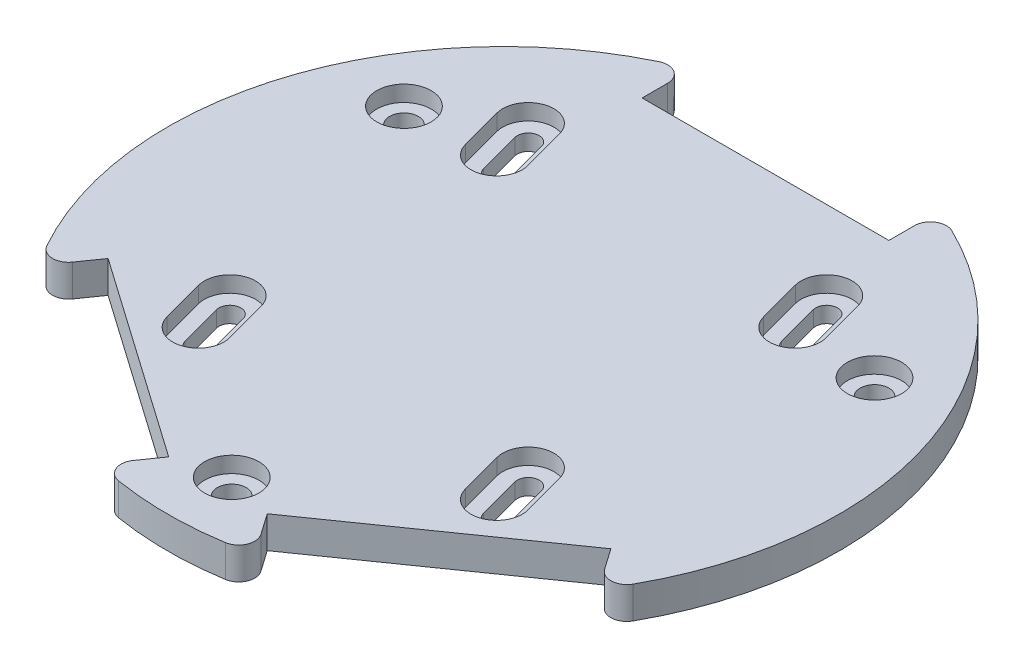
SolidWorks part; units mm, degrees
ref_plane "Plan de face" through (0, 0, 0) normal (0, 0, 1) x (1, 0, 0)
ref_plane "Plan de dessus" through (0, 0, 0) normal (0, 1, 0) x (1, 0, 0)
ref_plane "Plan de droite" through (0, 0, 0) normal (1, 0, 0) x (0, 0, -1)
sketch "Sketch1" plane through (0, 0, 0) normal (0, 1, 0) x (1, 0, 0)
  line L0 (0, 0) -> (0, 41) construction
  line L1 (0, 0) -> (-23.5166, -33.5852) construction
  line L2 (0, 0) -> (23.5166, -33.5852) construction
  line L3 (-39.3263, -22.5152) -> (-7.707, -44.6553)
  line L4 (7.707, -44.6553) -> (39.3263, -22.5152)
  line L5 (-19.3, 41) -> (19.3, 41)
  line L6 (-19.3, 41) -> (-19.3, 48.8238)
  line L8 (19.3, 41) -> (19.3, 48.8238)
  line L9 (7.707, -44.6553) -> (12.1945, -51.0641)
  line L11 (39.3263, -22.5152) -> (43.8138, -28.9241)
  line L12 (-7.707, -44.6553) -> (-12.1945, -51.0641)
  line L13 (-39.3263, -22.5152) -> (-43.8138, -28.9241)
  line L14 (0, 0) -> (0, -42.5) construction
  line L15 (0, 0) -> (-36.8061, 21.25) construction
  line L16 (0, 0) -> (36.8061, 21.25) construction
  arc A0 (-19.3, 48.8238) -> (-43.8138, -28.9241) centre (0, 0) ccw
  arc A1 (43.8138, -28.9241) -> (19.3, 48.8238) centre (0, 0) ccw
  circle A3 centre (-36.8061, 21.25) radius 2.25 construction
  circle A4 centre (36.8061, 21.25) radius 2.25 construction
  circle A6 centre (0, -42.5) radius 2.25 construction
  arc A7 (-12.1945, -51.0641) -> (12.1945, -51.0641) centre (0, 0) ccw
  circle A8 centre (-36.8061, 21.25) radius 4.25
  circle A9 centre (36.8061, 21.25) radius 4.25
  circle A10 centre (0, -42.5) radius 4.25
  point P25 (23.5166, -33.5852)
  point P26 (-23.5166, -33.5852)
  dimension "D1" = 105
  dimension "D5" = 35
  dimension "D6" = 38.6
  dimension "D10" = 4.5
  dimension "D4" = 8.5
  dimension "D9" = 42.5
  dimension "D2" = 35
  dimension "D3" = 41
  dimension "D7" = 120
  dimension "D8" = 120
extrude "Boss-Extrude1" add sketch "Sketch1" along normal blind 5 contours L4 A0 L5 L3 | A8 | A9 | A10 region at (0, 0, -1.6057) region at (-36.8061, 0, -21.25) region at (36.8061, 0, -21.25) region at (0, 0, 42.5)
sketch "Esquisse1" plane through (0, 5, 0) normal (0, 1, 0) x (1, 0, 0)
  line L0 (0, 0) -> (-23.3345, 23.3345) construction
  line L1 (0, 0) -> (0, 41) construction
  line L2 (-19.3, 41) -> (19.3, 41) construction
  line L3 (-24.758, 28.6471) -> (-22.9463, 21.8856) construction
  line L4 (-23.116, 29.0871) -> (-21.3042, 22.3256)
  line L5 (-26.4001, 28.2071) -> (-24.5884, 21.4456)
  line L6 (0, 0) -> (23.3345, 23.3345) construction
  line L7 (0, 0) -> (23.3345, -23.3345) construction
  line L8 (0, 0) -> (-23.3345, -23.3345) construction
  line L9 (23.7228, 21.8856) -> (21.911, 28.6471) construction
  line L10 (22.0807, 21.4456) -> (20.2689, 28.2071)
  line L11 (25.3648, 22.3256) -> (23.5531, 29.0871)
  line L12 (23.7228, -24.7834) -> (21.911, -18.0219) construction
  line L13 (22.0807, -25.2234) -> (20.2689, -18.4619)
  line L14 (25.3648, -24.3434) -> (23.5531, -17.5819)
  line L15 (-22.9463, -24.7834) -> (-24.758, -18.0219) construction
  line L16 (-24.5884, -25.2234) -> (-26.4001, -18.4619)
  line L17 (-21.3042, -24.3434) -> (-23.116, -17.5819)
  line L18 (0, 0) -> (-10.9859, 41) construction
  line L19 (-22.9463, 21.8856) -> (-24.758, 28.6471) construction
  line L20 (-26.81, 20.8504) -> (-28.6217, 27.6118)
  line L21 (-19.0826, 22.9209) -> (-20.8943, 29.6824)
  line L22 (23.7228, 21.8856) -> (21.911, 28.6471) construction
  line L23 (19.859, 20.8504) -> (18.0473, 27.6118)
  line L24 (27.5865, 22.9209) -> (25.7747, 29.6824)
  line L25 (23.7228, -24.7834) -> (21.911, -18.0219) construction
  line L26 (19.859, -25.8187) -> (18.0473, -19.0572)
  line L27 (27.5865, -23.7481) -> (25.7747, -16.9867)
  line L28 (-22.9463, -24.7834) -> (-24.758, -18.0219) construction
  line L29 (-26.81, -25.8187) -> (-28.6217, -19.0572)
  line L30 (-19.0826, -23.7481) -> (-20.8943, -16.9867)
  arc A0 (-23.116, 29.0871) -> (-26.4001, 28.2071) centre (-24.758, 28.6471) ccw
  arc A1 (-24.5884, 21.4456) -> (-21.3042, 22.3256) centre (-22.9463, 21.8856) ccw
  arc A2 (22.0807, 21.4456) -> (25.3648, 22.3256) centre (23.7228, 21.8856) ccw
  arc A3 (23.5531, 29.0871) -> (20.2689, 28.2071) centre (21.911, 28.6471) ccw
  arc A4 (22.0807, -25.2234) -> (25.3648, -24.3434) centre (23.7228, -24.7834) ccw
  arc A5 (23.5531, -17.5819) -> (20.2689, -18.4619) centre (21.911, -18.0219) ccw
  arc A6 (-24.5884, -25.2234) -> (-21.3042, -24.3434) centre (-22.9463, -24.7834) ccw
  arc A7 (-23.116, -17.5819) -> (-26.4001, -18.4619) centre (-24.758, -18.0219) ccw
  arc A8 (-26.81, 20.8504) -> (-19.0826, 22.9209) centre (-22.9463, 21.8856) ccw
  arc A9 (-20.8943, 29.6824) -> (-28.6217, 27.6118) centre (-24.758, 28.6471) ccw
  arc A10 (19.859, 20.8504) -> (27.5865, 22.9209) centre (23.7228, 21.8856) ccw
  arc A11 (25.7747, 29.6824) -> (18.0473, 27.6118) centre (21.911, 28.6471) ccw
  arc A12 (19.859, -25.8187) -> (27.5865, -23.7481) centre (23.7228, -24.7834) ccw
  arc A13 (25.7747, -16.9867) -> (18.0473, -19.0572) centre (21.911, -18.0219) ccw
  arc A14 (-26.81, -25.8187) -> (-19.0826, -23.7481) centre (-22.9463, -24.7834) ccw
  arc A15 (-20.8943, -16.9867) -> (-28.6217, -19.0572) centre (-24.758, -18.0219) ccw
  point P8 (-23.8522, 25.2664)
  point P18 (22.8169, 25.2664)
  point P25 (22.8169, -21.4027)
  point P30 (-23.8522, -21.4027)
  point P40 (-23.8522, 25.2664)
  point P45 (22.8169, 25.2664)
  point P52 (22.8169, -21.4027)
  point P59 (-23.8522, -21.4027)
  dimension "D5" = 1.7
  dimension "D9" = 4
  dimension "D1" = 1.5
  dimension "D2" = 5.5
  dimension "D3" = 15
  dimension "D4" = 33
  dimension "D6" = 45
  dimension "D7" = 1.5
  dimension "D8" = 30
extrude "Enlèv. mat.-Extru.1" cut sketch "Esquisse1" against normal up to next contours L5 A1 L4 A0 | L11 A3 L10 A2 | L14 A5 L13 A4 | L17 A7 L16 A6 region at (-23.8522, 5, -25.2664) region at (22.8169, 5, -25.2664) region at (22.8169, 5, 21.4027) region at (-23.8522, 5, 21.4027)
extrude "Enlèv. mat.-Extru.2" cut sketch "Esquisse1<3>" against normal blind 2.5
sketch "Esquisse1<3>" plane through (0, 5, 0) normal (0, 1, 0) x (1, 0, 0) same geometry as "Esquisse1"
extrude "Enlèv. mat.-Extru.3" cut sketch "Sketch1<3>" against normal blind 2.5 from surface contours A8 | A9 | A10 region at (-36.8061, 0, -21.25) region at (36.8061, 0, -21.25) region at (0, 0, 42.5) starting at face at (-23.8522, 5, 21.4027)
sketch "Sketch1<3>" plane through (0, 0, 0) normal (0, 1, 0) x (1, 0, 0) same geometry as "Sketch1"
sketch "Esquisse4" plane through (0, 5, 0) normal (0, 1, 0) x (1, 0, 0)
  point P0 (0, -42.5)
  point P3 (36.8061, 21.25)
  point P6 (-36.8061, 21.25)
hole_wizard "M4 Clearance Hole1" positions "Esquisse4" profile "Esquisse3" hole size "M4" standard "ANSI Metric" end condition up to next
sketch "Esquisse3" plane through (0, 5, 42.5) normal (1, 0, 0) x (0, 0, 1)
  line L0 (0, 0) -> (0, 5)
  line L1 (0, 5) -> (2.25, 5)
  line L2 (2.25, 5) -> (2.25, 0)
  line L5 (2.25, 0) -> (0, 0)
  line L11 (0, -6.35) -> (0, 107.95) construction
  dimension "Thru Hole Dia." = 4.5
  dimension "Thru Hole Depth" = 5
fillet "Congé1" radius 2.5 6 edges at (19.3, 2.5, -48.8238) (-19.3, 2.5, -48.8238) (-43.8138, 2.5, 28.9241) (43.8138, 2.5, 28.9241) (12.1945, 2.5, 51.0641) (-12.1945, 2.5, 51.0641)
